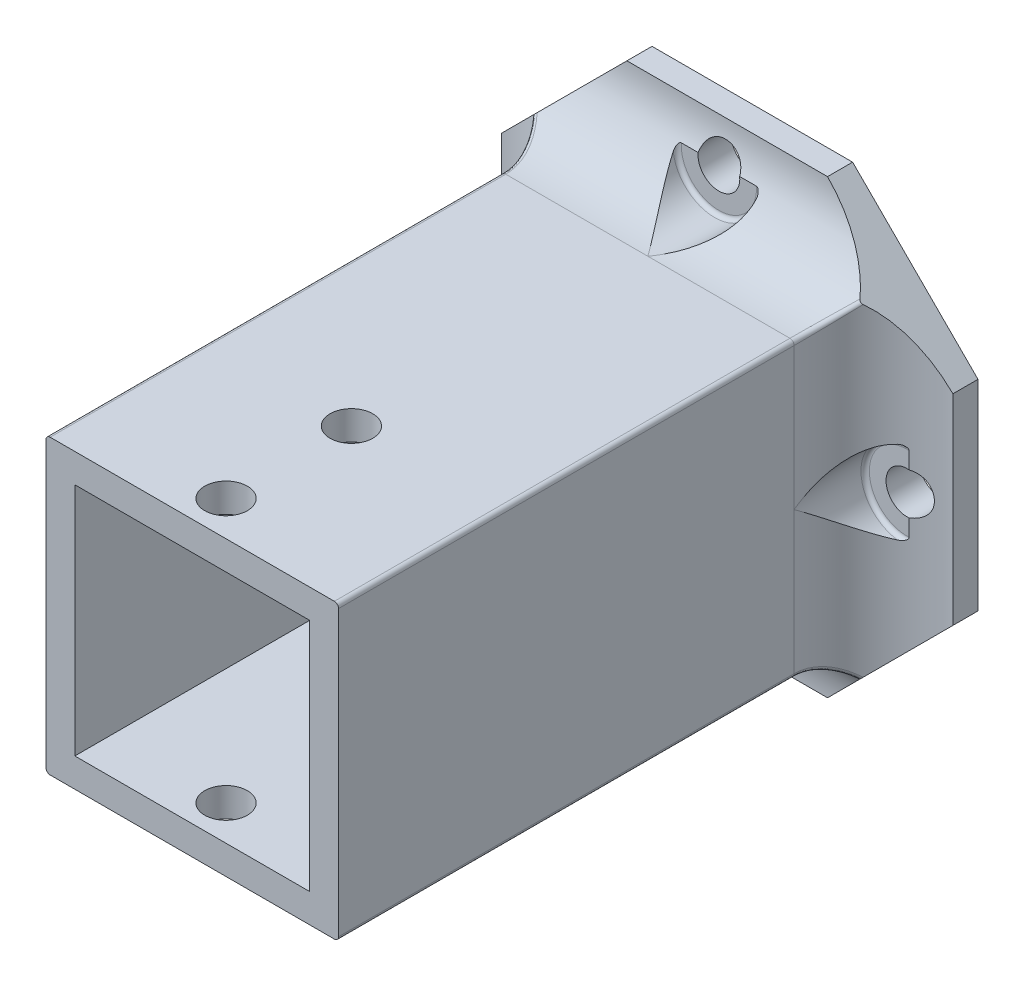
SolidWorks part; units mm, degrees
ref_plane "前视基准面" through (0, 0, 0) normal (0, 0, 1) x (1, 0, 0)
ref_plane "上视基准面" through (0, 0, 0) normal (0, 1, 0) x (1, 0, 0)
ref_plane "右视基准面" through (0, 0, 0) normal (1, 0, 0) x (0, 0, -1)
other "Configuration Table"
sketch "草图1" plane through (0, 0, 0) normal (0, 0, 1) x (1, 0, 0)
  line L1 (14.2, -14.2) -> (-14.2, -14.2)
  line L2 (14.2, -14.2) -> (14.2, 14.2)
  line L3 (14.2, 14.2) -> (-14.2, 14.2)
  line L4 (-14.2, -14.2) -> (-14.2, 14.2)
  line L5 (14.2, -14.2) -> (-14.2, 14.2) construction
  line L6 (14.2, 14.2) -> (-14.2, -14.2) construction
  point P0 (0, 0)
  dimension "D1" = 28.4
  dimension "D2" = 28.4
extrude "凸台-拉伸1" add sketch "草图1" along normal blind 3
sketch "草图2" plane through (0, 0, 3) normal (0, 0, 1) x (1, 0, 0)
  circle A0 centre (0, 0) radius 1
extrude "切除-拉伸1" cut sketch "草图2" against normal blind 3
sketch "草图5" plane through (0, 0, 0) normal (0, 0, -1) x (-1, 0, 0)
  circle A0 centre (0, 22.5) radius 2.5
  circle A1 centre (22.5, 0) radius 2.5
  circle A2 centre (-22.5, 0) radius 2.5
  circle A3 centre (0, -22.5) radius 2.5
sketch "草图6" plane through (0, 0, 3) normal (0, 0, 1) x (1, 0, 0)
  line L0 (12, 27) -> (27, 12)
  line L1 (27, -27) -> (-27, -27)
  line L2 (27, -27) -> (27, 27)
  line L3 (27, 27) -> (-27, 27)
  line L4 (-27, -27) -> (-27, 27)
  line L5 (27, -27) -> (-27, 27) construction
  line L6 (27, 27) -> (-27, -27) construction
  line L7 (27, -12) -> (12, -27)
  line L8 (-12, -27) -> (-27, -12)
  line L9 (-27, 12) -> (-12, 27)
  point P0 (0, 0)
  line M6 (-14.2, 14.2) -> (-14.2, -14.2)
  line M7 (-14.2, -14.2) -> (14.2, -14.2)
  line M8 (14.2, -14.2) -> (14.2, 14.2)
  line M9 (14.2, 14.2) -> (-14.2, 14.2)
  dimension "D1" = 4.5
  dimension "D2" = 15
  dimension "D3" = 15
  dimension "D4" = 15
  dimension "D5" = 15
  dimension "D6" = 15
  dimension "D7" = 15
  dimension "D8" = 15
  dimension "D9" = 15
extrude "凸台-拉伸3" add sketch "草图6" against normal blind 3 contours L9 L4 L8 L1 L7 L2 L0 L3 M6 M9 M8 M7 region at (18.96, 18.96, 3)
extrude "切除-拉伸2" cut sketch "草图5" against normal blind 3
sketch "草图7" plane through (0, 0, 3) normal (0, 0, 1) x (1, 0, 0)
  line L1 (17.5, -17.5) -> (-17.5, -17.5)
  line L3 (17.5, -17.5) -> (17.5, 17.5)
  line L4 (17.5, 17.5) -> (-17.5, 17.5)
  line L5 (-17.5, -17.5) -> (-17.5, 17.5)
  line L6 (17.5, -17.5) -> (-17.5, 17.5) construction
  line L15 (17.5, 17.5) -> (-17.5, -17.5) construction
  line L16 (14.05, -14.05) -> (-14.05, -14.05)
  line L21 (14.05, -14.05) -> (14.05, 14.05)
  line L22 (14.05, 14.05) -> (-14.05, 14.05)
  line L23 (-14.05, -14.05) -> (-14.05, 14.05)
  line L24 (14.05, -14.05) -> (-14.05, 14.05) construction
  line L25 (14.05, 14.05) -> (-14.05, -14.05) construction
  point P0 (0, 0)
  point P7 (0, 0)
  dimension "D1" = 28.1
  dimension "D2" = 28.1
  dimension "D3" = 35
  dimension "D4" = 35
extrude "凸台-拉伸4" add sketch "草图7" along normal blind 73 contours L5 L1 L3 L4 L16 L23 L22 L21 region at (0, -17.005, 3)
sketch "草图8" plane through (-17.5, 0, 0) normal (-1, 0, 0) x (0, 0, 1)
  line L0 (67, 17.5) -> (67, -17.5)
  line L4 (67, 17.5) -> (76, 17.5)
  line L5 (67, 17.5) -> (67, -17.5)
  line L6 (67, -17.5) -> (76, -17.5)
  line L7 (76, 17.5) -> (76, -17.5)
  point P2 (76, 17.5)
  point P3 (76, -17)
  point P4 (76, -17.5)
  point P8 (0, 0)
  point P10 (76, 17)
  point P11 (0, 0)
  point P12 (74.5839, -17)
  point P13 (0, 0)
  point P14 (0, 0)
  point P16 (0, 0)
  dimension "D1" = 9
sketch "草图9" plane through (0, -17.5, 0) normal (0, -1, 0) x (1, 0, 0)
  circle A0 centre (-0.1414, 62.82) radius 2.55
  circle A1 centre (-0.1414, 47.82) radius 2.55
extrude "切除-拉伸3" cut sketch "草图8" against normal blind 73 contours L0 region at (-17.5, 0, 71.5)
extrude "切除-拉伸4" cut sketch "草图9" against normal blind 73
fillet "圆角4" radius 9.5 4 edges at (0, -17.5, 3) (-17.5, 0, 3) (0, 17.5, 3) (17.5, 0, 3)
sketch "草图10" plane through (0, 0, 0) normal (0, 0, -1) x (-1, 0, 0)
  circle A0 centre (0, 22.5) radius 5
  circle A1 centre (22.5, 0) radius 5
  circle A2 centre (0, -22.5) radius 5
  circle A3 centre (-22.5, 0) radius 5
  point P3 (0, 0)
  point P12 (0, 0)
  dimension "D1" = 10
  dimension "D2" = 4
extrude "切除-拉伸6" cut sketch "草图10" against normal blind 10 from offset 4 offset against normal yes
fillet "圆角6" radius 0.5 12 edges at (17.5, 0, 4) (0, -17.5, 4) (-17.5, 0, 4) (0, 17.5, 4) (18.0139, 18.0139, 9.4178) (18.0139, -18.0139, 9.4178) (-18.0139, -18.0139, 9.4178) (-18.0139, 18.0139, 9.4178) (17.5, 17.5, 39.75) (17.5, -17.5, 39.75) (-17.5, -17.5, 39.75) (-17.5, 17.5, 39.75)
